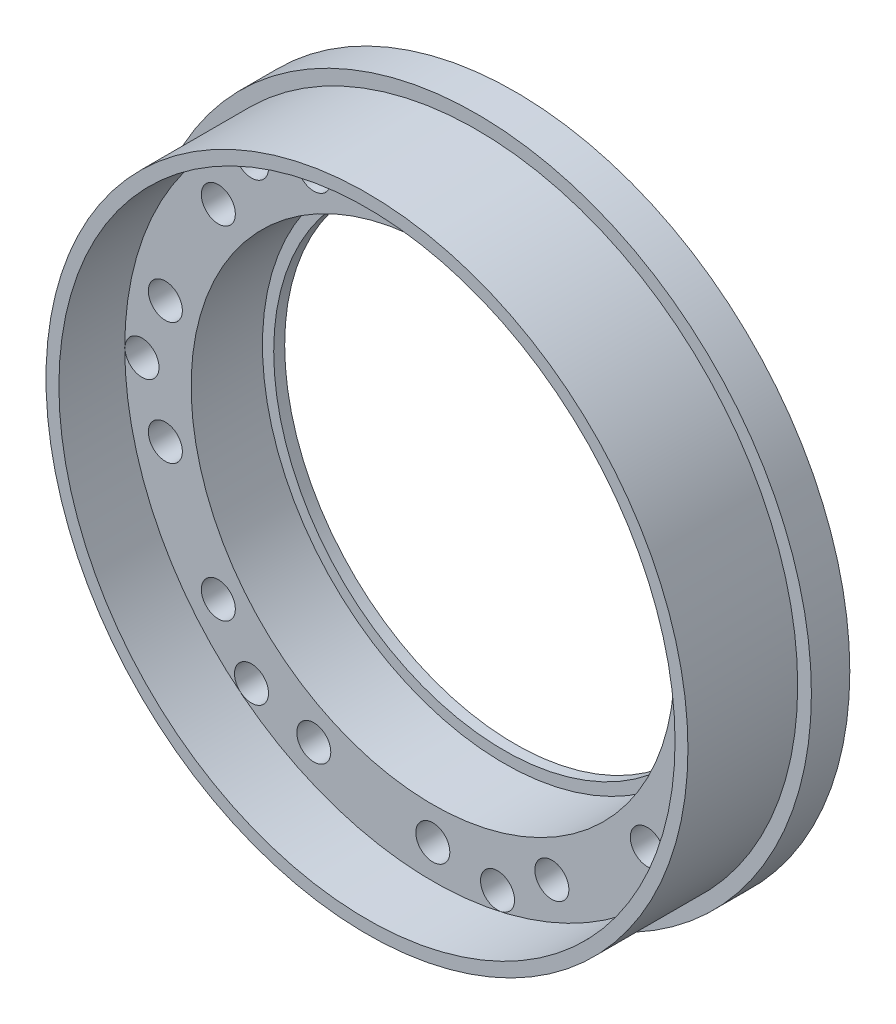
SolidWorks part; units mm, degrees
material "6061 Alloy"
ref_plane "Front Plane" through (0, 0, 0) normal (0, 0, 1) x (1, 0, 0)
ref_plane "Top Plane" through (0, 0, 0) normal (0, 1, 0) x (1, 0, 0)
ref_plane "Right Plane" through (0, 0, 0) normal (1, 0, 0) x (0, 0, -1)
sketch "Sketch1" plane through (0, 0, 0) normal (0, 0, 1) x (1, 0, 0)
  line L0 (0, 0) -> (0, 34.3477) construction
  circle A0 centre (0, 0) radius 29.25
  circle A1 centre (0, 0) radius 30.5
  circle A2 centre (0, 0) radius 22.025
  circle A3 centre (0, 25) radius 1.55
  circle A4 centre (10.8471, 22.5242) radius 1.55
  circle A5 centre (19.5458, 15.5872) radius 1.55
  circle A6 centre (24.3732, 5.563) radius 1.55
  circle A7 centre (24.3732, -5.563) radius 1.55
  circle A8 centre (19.5458, -15.5872) radius 1.55
  circle A9 centre (10.8471, -22.5242) radius 1.55
  circle A10 centre (0, -25) radius 1.55
  circle A11 centre (-10.8471, -22.5242) radius 1.55
  circle A12 centre (-19.5458, -15.5872) radius 1.55
  circle A13 centre (-24.3732, -5.563) radius 1.55
  circle A14 centre (-24.3732, 5.563) radius 1.55
  circle A15 centre (-19.5458, 15.5872) radius 1.55
  circle A16 centre (-10.8471, 22.5242) radius 1.55
  point P29 (0, 0)
  dimension "D1" = 58.5
  dimension "D2" = 61
  dimension "D3" = 44.05
  dimension "D5" = 3.1
  dimension "D6" = 14
  dimension "D4" = 25
extrude "Boss-Extrude1" add sketch "Sketch1" along normal blind 3.5 contours A0 A1 | A2 A3 A0 A16 A15 A14 A13 A12 A11 A10 A9 A8 A7 A6 A5 A4 | A13 | A14 | A15 | A16 | L0 A3 | A3 L0 | A4 | A5 | A6 | A7 | A8 | A9 | A10 | A11 | A12 region at (20.0979, 20.0979, 0) region at (20.9568, 20.9568, 0) region at (-0.6578, 25, 0) region at (0.6578, 25, 0) region at (10.8471, 22.5242, 0) region at (19.5458, 15.5872, 0) region at (24.3732, 5.563, 0) region at (24.3732, -5.563, 0) region at (19.5458, -15.5872, 0) region at (10.8471, -22.5242, 0) region at (0, -25, 0) region at (-10.8471, -22.5242, 0) region at (-19.5458, -15.5872, 0) region at (-24.3732, -5.563, 0) region at (-24.3732, 5.563, 0) region at (-19.5458, 15.5872, 0) region at (-10.8471, 22.5242, 0)
extrude "lapvsrotor" add sketch "Sketch1<8>" along normal blind 10 from surface contours A2 A3 A0 A16 A15 A14 A13 A12 A11 A10 A9 A8 A7 A6 A5 A4 | A13 | A12 | A11 | A10 | A9 | A7 | A6 | A5 | A4 | A3 L0 | L0 A3 | A16 | A15 | A14 | A8 region at (20.0979, 20.0979, 0) region at (-0.6578, 25, 0) region at (0.6578, 25, 0) region at (10.8471, 22.5242, 0) region at (19.5458, 15.5872, 0) region at (24.3732, 5.563, 0) region at (24.3732, -5.563, 0) region at (19.5458, -15.5872, 0) region at (10.8471, -22.5242, 0) region at (0, -25, 0) region at (-10.8471, -22.5242, 0) region at (-19.5458, -15.5872, 0) region at (-24.3732, -5.563, 0) region at (-24.3732, 5.563, 0) region at (-19.5458, 15.5872, 0) region at (-10.8471, 22.5242, 0) starting at face at (30.5, 0, 3.5)
sketch "Sketch1<8>" plane through (0, 0, 0) normal (0, 0, 1) x (1, 0, 0) same geometry as "Sketch1"
extrude "Cut-Extrude1" cut sketch "Sketch1<9>" against normal blind 10 from surface contours A13 | A12 | A11 | A10 | A9 | A8 | A14 | A15 | A16 | A4 | A5 | A6 | A7 | A3 region at (10.8471, 22.5242, 0) region at (19.5458, 15.5872, 0) region at (24.3732, 5.563, 0) region at (24.3732, -5.563, 0) region at (19.5458, -15.5872, 0) region at (10.8471, -22.5242, 0) region at (0, -25, 0) region at (-10.8471, -22.5242, 0) region at (-19.5458, -15.5872, 0) region at (-24.3732, -5.563, 0) region at (-24.3732, 5.563, 0) region at (-19.5458, 15.5872, 0) region at (-10.8471, 22.5242, 0) starting at face at (29.25, 0, 13.5)
sketch "Sketch1<9>" plane through (0, 0, 0) normal (0, 0, 1) x (1, 0, 0) same geometry as "Sketch1"
sketch "Sketch2" plane through (0, 0, 0) normal (0, 0, 1) x (1, 0, 0)
  circle A0 centre (0, 0) radius 22.05
  circle A1 centre (0, 0) radius 21
  dimension "D1" = 44.1
  dimension "D2" = 42
extrude "Boss-Extrude3" add sketch "Sketch2" along normal blind 1 from surface starting at face at (30.5, 0, 0)
sketch "Sketch3" plane through (0, 0, 0) normal (0, 0, 1) x (1, 0, 0)
  line L0 (0, 0) -> (0, 37.16) construction
  line L1 (0, 0) -> (8.6842, 38.0481) construction
  line L2 (0, 0) -> (39.9985, 19.2623) construction
  line L3 (0, 0) -> (41.5228, 0) construction
  circle A1 centre (0, 0) radius 26.5 construction
  circle A2 centre (5.8968, 25.8356) radius 1.55
  circle A15 centre (23.8757, 11.4979) radius 1.55
  circle A16 centre (23.8757, -11.4979) radius 1.55
  circle A17 centre (5.8968, -25.8356) radius 1.55
  circle A18 centre (-16.5225, -20.7185) radius 1.55
  circle A19 centre (-26.5, 0) radius 1.55
  circle A20 centre (-16.5225, 20.7185) radius 1.55
  point P27 (0, 0)
  point P28 (0, 0)
  dimension "D2" = 53
  dimension "D3" = 3.1
  dimension "D4" = 64.286
  dimension "D1" = 12.857
  dimension "D5" = 7
extrude "Cut-Extrude2" cut sketch "Sketch3" along normal through all from surface starting at face at (30.5, 0, 0)
sketch "Sketch4" plane through (0, 0, 0) normal (0, 0, 1) x (1, 0, 0)
  circle A0 centre (0, 0) radius 28.075
  circle A1 centre (0, 0) radius 21
  dimension "D1" = 56.15
  dimension "D2" = 42
extrude "Cut-Extrude3" cut sketch "Sketch4" against normal blind 6 from surface starting at face at (7.4468, 25.8356, 13.5)
sketch "Sketch5" plane through (0, 0, 0) normal (0, 0, 1) x (1, 0, 0)
  circle A0 centre (5.8968, 25.8356) radius 3
  dimension "D1" = 6
extrude "Cut-Extrude4" cut sketch "Sketch5" along normal blind 2.5 from surface starting at face at (7.4468, 25.8356, 0)
pattern_circular "CirPattern1" count 7 over 360 about axis through (0, 0, 3.5) along (0, 0, -1) of "Cut-Extrude4"
